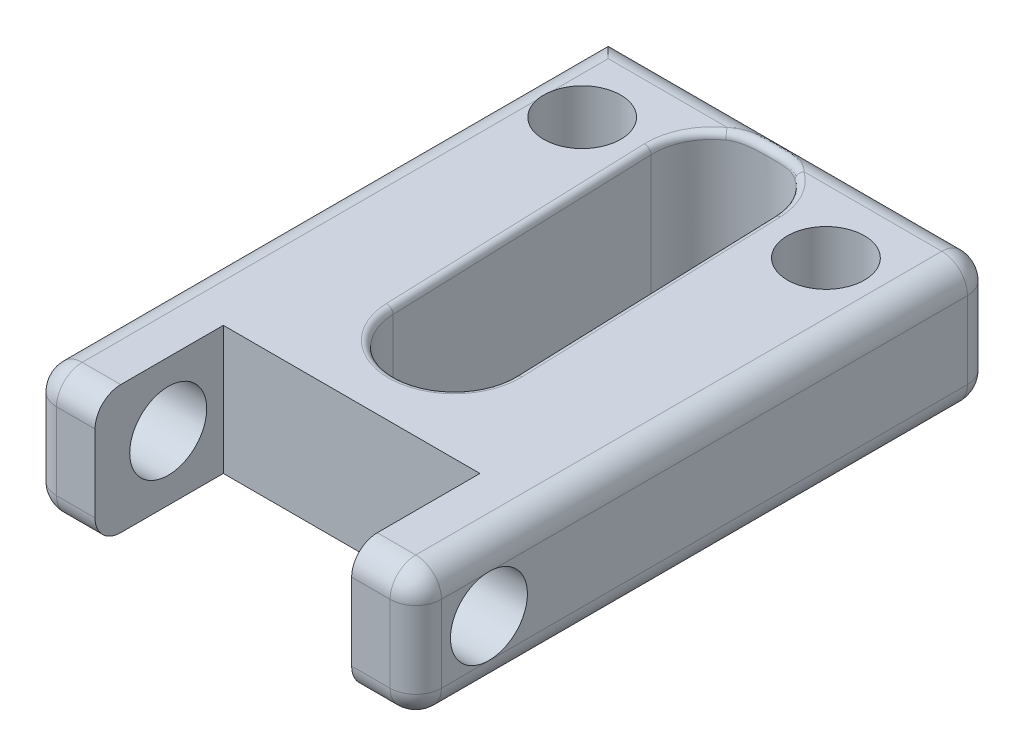
SolidWorks part; units mm, degrees
ref_plane "Front Plane" through (0, 0, 0) normal (0, 0, 1) x (1, 0, 0)
ref_plane "Top Plane" through (0, 0, 0) normal (0, 1, 0) x (1, 0, 0)
ref_plane "Right Plane" through (0, 0, 0) normal (1, 0, 0) x (0, 0, -1)
sketch "Sketch1" plane through (0, 0, 0) normal (0, 1, 0) x (1, 0, 0)
  line L1 (-15, 22.5) -> (15, 22.5)
  line L2 (-15, 22.5) -> (-15, -22.5)
  line L3 (-15, -22.5) -> (15, -22.5)
  line L4 (15, 22.5) -> (15, -22.5)
  line L5 (-15, 22.5) -> (15, -22.5) construction
  line L6 (-15, -22.5) -> (15, 22.5) construction
  point P0 (0, 0)
  dimension "D1" = 45
  dimension "D2" = 30
extrude "Boss-Extrude1" add sketch "Sketch1" along normal blind 10
sketch "Sketch2" plane through (0, 10, 0) normal (0, 1, 0) x (1, 0, 0)
  line L0 (-0.7255, 16.341) -> (0, -4.5) construction
  line L1 (3.893, 16.5018) -> (4.6186, -4.3392)
  line L2 (-5.3441, 16.1802) -> (-4.6186, -4.6608)
  line L3 (-15, -22.5) -> (15, -22.5) construction
  line L4 (-10, -22.5) -> (10, -22.5)
  line L5 (-10, -22.5) -> (-10, -12.5)
  line L6 (-10, -12.5) -> (10, -12.5)
  line L7 (10, -22.5) -> (10, -12.5)
  line L8 (-15, 22.5) -> (-15, -22.5) construction
  line L9 (15, -22.5) -> (15, 22.5) construction
  arc A0 (3.893, 16.5018) -> (-5.3441, 16.1802) centre (-0.7255, 16.341) ccw
  arc A1 (-4.6186, -4.6608) -> (4.6186, -4.3392) centre (0, -4.5) ccw
  point P2 (-0.3628, 5.9205)
  point P17 (0, -12.5)
  point P18 (-0.7775, 14.896)
  point P19 (-1.2572, 5.8986)
  point P20 (0, 0)
  point P21 (0, 0)
  point P22 (0, -4.5)
  point P23 (0, 16.3663)
  point P24 (0, -4.5)
  dimension "D1" = 5
  dimension "D2" = 5
  dimension "D3" = 10
  dimension "D4" = 8
  dimension "D5" = 20
extrude "Cut-Extrude1" cut sketch "Sketch2" against normal through all
fillet "Fillet1" radius 2 13 edges at (0, 10, -22.5) (0, 0, -22.5) (15, 5, -22.5) (15, 0, 0) (12.5, 0, 22.5) (-12.5, 0, 22.5) (-15, 5, 22.5) (-15, 0, 0) (15, 5, 22.5) (12.5, 10, 22.5) (-12.5, 10, 22.5) (-15, 10, 0) (15, 10, 0)
fillet "Fillet3" radius 0.5 6 edges at (3.1471, 10, -18.8629) (-4.6835, 10, -18.7266) (4.2558, 10, -6.0813) (0.1608, 10, 9.1186) (-4.9813, 10, -5.7597) (-0.1714, 9.9534, -20.929)
sketch "Sketch3" plane through (15, 0, 0) normal (1, 0, 0) x (0, 0, -1)
  circle A0 centre (-16.7972, 5.024) radius 3
  point P2 (-17.1337, 5.3124)
  point P3 (-16.7972, 5.024)
  dimension "D1" = 6
extrude "Cut-Extrude2" cut sketch "Sketch3" against normal through all
sketch "Sketch4" plane through (0, 10, 0) normal (0, 1, 0) x (1, 0, 0)
  circle A0 centre (8.9355, 15.5359) radius 3
  circle A1 centre (-10.0645, 15.5359) radius 3
  dimension "D1" = 6
  dimension "D2" = 2
extrude "Cut-Extrude3" cut sketch "Sketch4" against normal blind 20
